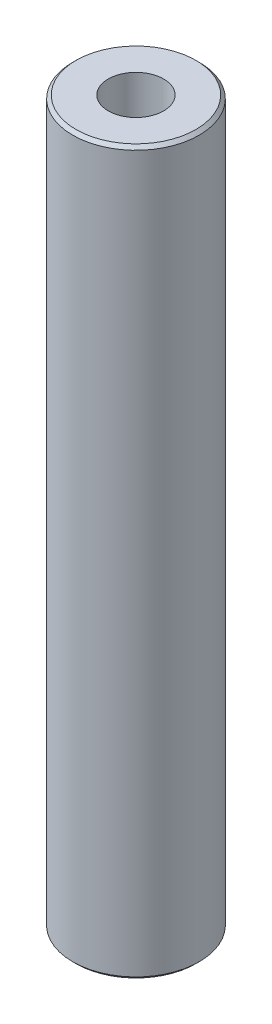
SolidWorks part; units mm, degrees
ref_plane "Front Plane" through (0, 0, 0) normal (0, 0, 1) x (1, 0, 0)
ref_plane "Top Plane" through (0, 0, 0) normal (0, 1, 0) x (1, 0, 0)
ref_plane "Right Plane" through (0, 0, 0) normal (1, 0, 0) x (0, 0, -1)
sketch "Sketch1" plane through (0, 0, 0) normal (0, 1, 0) x (1, 0, 0)
  circle A0 centre (0, 0) radius 52.5
  dimension "SHAFT_OD" = 105
extrude "Boss-Extrude1" add sketch "Sketch1" along normal blind 600
sketch "Sketch2" plane through (0, 0, 0) normal (0, 1, 0) x (1, 0, 0)
  circle A0 centre (0, 0) radius 23.0073
  dimension "BORE_D" = 46.0147
extrude "Cut-Extrude1" cut sketch "Sketch2" along normal through all
chamfer "Chamfer1" distance 2.716 angle 45 2 edges at (0, 600, 52.5) (0, 0, 52.5)
